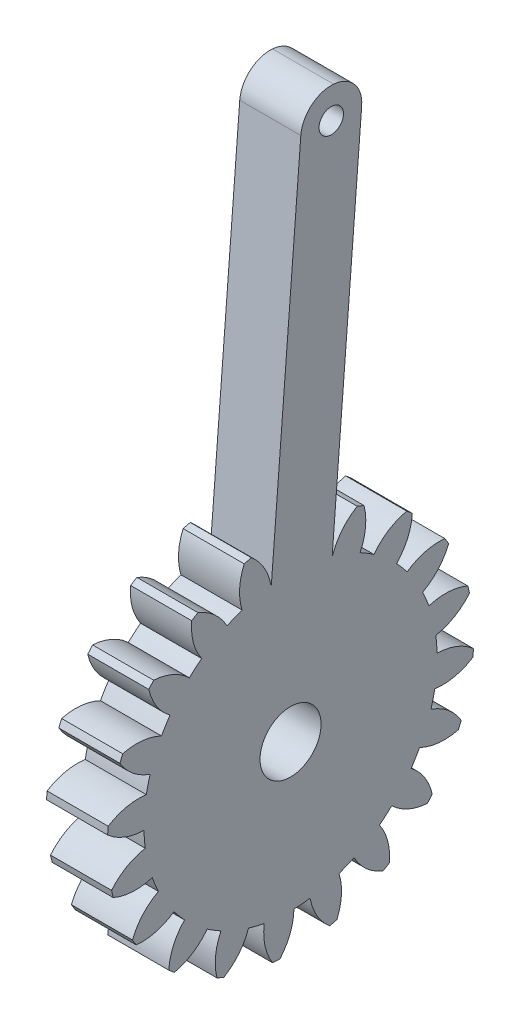
SolidWorks part; units mm, degrees
ref_plane "前视基准面" through (0, 0, 0) normal (0, 0, 1) x (1, 0, 0)
ref_plane "上视基准面" through (0, 0, 0) normal (0, 1, 0) x (1, 0, 0)
ref_plane "右视基准面" through (0, 0, 0) normal (1, 0, 0) x (0, 0, -1)
other "Configuration Table"
sketch "草图1" plane through (0, 0, 0) normal (1, 0, 0) x (0, 0, -1)
  line L0 (0, 0) -> (50000, 0) construction
  line L1 (0, 27) -> (0, -50000) construction
  line L2 (0, 0) -> (8.2085, 22.5526) construction
  line L3 (0, 0) -> (3922.9548, 49845.8667) construction
  arc A0 (-7.9429, 22.6475) -> (-10.3978, 21.6307) centre (0, 0) ccw
  arc A5 (1.751, 29.9489) -> (-0.5557, 23.9936) centre (8.6776, 23.8416) ccw
  arc A6 (2.9556, 29.8541) -> (4.3022, 23.6112) centre (-4.8411, 24.9056) cw
  arc A7 (2.9556, 29.8541) -> (1.751, 29.9489) centre (0, 0) ccw
  arc A8 (12.0363, 27.4796) -> (11.3879, 21.1262) centre (3.092, 25.1826) cw
  arc A9 (12.0363, 27.4796) -> (10.92, 27.942) centre (0, 0) ccw
  arc A10 (10.92, 27.942) -> (6.886, 22.9909) centre (15.6204, 19.9932) ccw
  arc A11 (19.9389, 22.4152) -> (17.3589, 16.5731) centre (10.7225, 22.9946) cw
  arc A12 (19.9389, 22.4152) -> (19.0201, 23.1999) centre (0, 0) ccw
  arc A13 (19.0201, 23.1999) -> (13.6535, 19.7378) centre (21.0341, 14.1877) ccw
  arc A14 (25.8897, 15.1566) -> (21.6307, 10.3978) centre (17.3035, 18.5557) cw
  arc A15 (25.8897, 15.1566) -> (25.2583, 16.1869) centre (0, 0) ccw
  arc A16 (25.2583, 16.1869) -> (19.0846, 14.5526) centre (24.3888, 6.9934) ccw
  arc A17 (29.3062, 6.4145) -> (23.7851, 3.2046) centre (22.1906, 12.3004) cw
  arc A18 (29.3062, 6.4145) -> (29.0241, 7.5894) centre (0, 0) ccw
  arc A19 (29.0241, 7.5894) -> (22.6475, 7.9429) centre (25.3562, -0.8855) ccw
  arc A20 (29.8541, -2.9556) -> (23.6112, -4.3022) centre (24.9056, 4.8411) cw
  arc A21 (29.8541, -2.9556) -> (29.9489, -1.751) centre (0, 0) ccw
  arc A22 (29.9489, -1.751) -> (23.9936, 0.5557) centre (23.8416, -8.6776) ccw
  arc A23 (27.4796, -12.0363) -> (21.1262, -11.3879) centre (25.1826, -3.092) cw
  arc A24 (27.4796, -12.0363) -> (27.942, -10.92) centre (0, 0) ccw
  arc A25 (27.942, -10.92) -> (22.9909, -6.886) centre (19.9932, -15.6204) ccw
  arc A26 (22.4152, -19.9389) -> (16.5731, -17.3589) centre (22.9946, -10.7225) cw
  arc A27 (22.4152, -19.9389) -> (23.1999, -19.0201) centre (0, 0) ccw
  arc A28 (23.1999, -19.0201) -> (19.7378, -13.6535) centre (14.1877, -21.0341) ccw
  arc A29 (15.1566, -25.8897) -> (10.3978, -21.6307) centre (18.5557, -17.3035) cw
  arc A30 (15.1566, -25.8897) -> (16.1869, -25.2583) centre (0, 0) ccw
  arc A31 (16.1869, -25.2583) -> (14.5526, -19.0846) centre (6.9934, -24.3888) ccw
  arc A32 (6.4145, -29.3062) -> (3.2046, -23.7851) centre (12.3004, -22.1906) cw
  arc A33 (6.4145, -29.3062) -> (7.5894, -29.0241) centre (0, 0) ccw
  arc A34 (7.5894, -29.0241) -> (7.9429, -22.6475) centre (-0.8855, -25.3562) ccw
  arc A35 (-2.9556, -29.8541) -> (-4.3022, -23.6112) centre (4.8411, -24.9056) cw
  arc A36 (-2.9556, -29.8541) -> (-1.751, -29.9489) centre (0, 0) ccw
  arc A37 (-1.751, -29.9489) -> (0.5557, -23.9936) centre (-8.6776, -23.8416) ccw
  arc A38 (-12.0363, -27.4796) -> (-11.3879, -21.1262) centre (-3.092, -25.1826) cw
  arc A39 (-12.0363, -27.4796) -> (-10.92, -27.942) centre (0, 0) ccw
  arc A40 (-10.92, -27.942) -> (-6.886, -22.9909) centre (-15.6204, -19.9932) ccw
  arc A41 (-19.9389, -22.4152) -> (-17.3589, -16.5731) centre (-10.7225, -22.9946) cw
  arc A42 (-19.9389, -22.4152) -> (-19.0201, -23.1999) centre (0, 0) ccw
  arc A43 (-19.0201, -23.1999) -> (-13.6535, -19.7378) centre (-21.0341, -14.1877) ccw
  arc A44 (-25.8897, -15.1566) -> (-21.6307, -10.3978) centre (-17.3035, -18.5557) cw
  arc A45 (-25.8897, -15.1566) -> (-25.2583, -16.1869) centre (0, 0) ccw
  arc A46 (-25.2583, -16.1869) -> (-19.0846, -14.5526) centre (-24.3888, -6.9934) ccw
  arc A47 (-29.3062, -6.4145) -> (-23.7851, -3.2046) centre (-22.1906, -12.3004) cw
  arc A48 (-29.3062, -6.4145) -> (-29.0241, -7.5894) centre (0, 0) ccw
  arc A49 (-29.0241, -7.5894) -> (-22.6475, -7.9429) centre (-25.3562, 0.8855) ccw
  arc A50 (-29.8541, 2.9556) -> (-23.6112, 4.3022) centre (-24.9056, -4.8411) cw
  arc A51 (-29.8541, 2.9556) -> (-29.9489, 1.751) centre (0, 0) ccw
  arc A52 (-29.9489, 1.751) -> (-23.9936, -0.5557) centre (-23.8416, 8.6776) ccw
  arc A53 (-27.4796, 12.0363) -> (-21.1262, 11.3879) centre (-25.1826, 3.092) cw
  arc A54 (-27.4796, 12.0363) -> (-27.942, 10.92) centre (0, 0) ccw
  arc A55 (-27.942, 10.92) -> (-22.9909, 6.886) centre (-19.9932, 15.6204) ccw
  arc A56 (-22.4152, 19.9389) -> (-16.5731, 17.3589) centre (-22.9946, 10.7225) cw
  arc A57 (-22.4152, 19.9389) -> (-23.1999, 19.0201) centre (0, 0) ccw
  arc A58 (-23.1999, 19.0201) -> (-19.7378, 13.6535) centre (-14.1877, 21.0341) ccw
  arc A59 (-15.1566, 25.8897) -> (-10.3978, 21.6307) centre (-18.5557, 17.3035) cw
  arc A60 (-15.1566, 25.8897) -> (-16.1869, 25.2583) centre (0, 0) ccw
  arc A61 (-16.1869, 25.2583) -> (-14.5526, 19.0846) centre (-6.9934, 24.3888) ccw
  arc A62 (-6.4145, 29.3062) -> (-3.2046, 23.7851) centre (-12.3004, 22.1906) cw
  arc A63 (-6.4145, 29.3062) -> (-7.5894, 29.0241) centre (0, 0) ccw
  arc A64 (-7.5894, 29.0241) -> (-7.9429, 22.6475) centre (0.8855, 25.3562) ccw
  arc A65 (-14.5526, 19.0846) -> (-16.5731, 17.3589) centre (0, 0) ccw
  arc A66 (-19.7378, 13.6535) -> (-21.1262, 11.3879) centre (0, 0) ccw
  arc A67 (-22.9909, 6.886) -> (-23.6112, 4.3022) centre (0, 0) ccw
  arc A68 (-23.9936, -0.5557) -> (-23.7851, -3.2046) centre (0, 0) ccw
  arc A69 (-19.0846, -14.5526) -> (-17.3589, -16.5731) centre (0, 0) ccw
  arc A70 (-22.6475, -7.9429) -> (-21.6307, -10.3978) centre (0, 0) ccw
  arc A71 (-13.6535, -19.7378) -> (-11.3879, -21.1262) centre (0, 0) ccw
  arc A72 (0.5557, -23.9936) -> (3.2046, -23.7851) centre (0, 0) ccw
  arc A73 (7.9429, -22.6475) -> (10.3978, -21.6307) centre (0, 0) ccw
  arc A74 (14.5526, -19.0846) -> (16.5731, -17.3589) centre (0, 0) ccw
  arc A75 (19.7378, -13.6535) -> (21.1262, -11.3879) centre (0, 0) ccw
  arc A76 (22.9909, -6.886) -> (23.6112, -4.3022) centre (0, 0) ccw
  arc A77 (23.9936, 0.5557) -> (23.7851, 3.2046) centre (0, 0) ccw
  arc A78 (22.6475, 7.9429) -> (21.6307, 10.3978) centre (0, 0) ccw
  arc A79 (19.0846, 14.5526) -> (17.3589, 16.5731) centre (0, 0) ccw
  arc A80 (13.6535, 19.7378) -> (11.3879, 21.1262) centre (0, 0) ccw
  arc A81 (6.886, 22.9909) -> (4.3022, 23.6112) centre (0, 0) ccw
  arc A82 (-0.5557, 23.9936) -> (-3.2046, 23.7851) centre (0, 0) ccw
  arc A83 (-6.886, -22.9909) -> (-4.3022, -23.6112) centre (0, 0) ccw
  point P134 (0, 0)
  dimension "D1" = 48
  dimension "D3" = 20
  dimension "D2" = 20
  dimension "D5" = 4.5
extrude "凸台-拉伸1" add sketch "草图1" along normal blind 10
sketch "草图2" plane through (10, 0, 0) normal (1, 0, 0) x (0, 0, -1)
  line L0 (0, 0) -> (0, 50000) construction
  line L5 (0, 0) -> (3922.9548, 49845.8667) construction
  line L6 (2.0767, 90.1149) -> (-4.9846, 0.3923)
  line L7 (-4.9846, 0.3923) -> (4.9846, -0.3923)
  line L8 (4.9846, -0.3923) -> (12.0459, 89.3303)
  line L9 (12.0459, 89.3303) -> (2.0767, 90.1149)
  dimension "D1" = 4.5
  dimension "D2" = 5
  dimension "D3" = 5
  dimension "D4" = 90
extrude "凸台-拉伸2" add sketch "草图2" against normal blind 10
fillet "圆角1" radius 5 2 edges at (5, 89.3303, -12.0459) (5, 90.1149, -2.0767)
sketch "草图3" plane through (10, 0, 0) normal (1, 0, 0) x (0, 0, -1)
  circle A0 centre (0, 0) radius 5
  dimension "D1" = 10
extrude "切除-拉伸1" cut sketch "草图3" against normal blind 10
sketch "草图4" plane through (10, 0, 0) normal (1, 0, 0) x (0, 0, -1)
  circle A0 centre (6.669, 84.738) radius 2
  dimension "D1" = 4
extrude "切除-拉伸2" cut sketch "草图4" against normal blind 10
